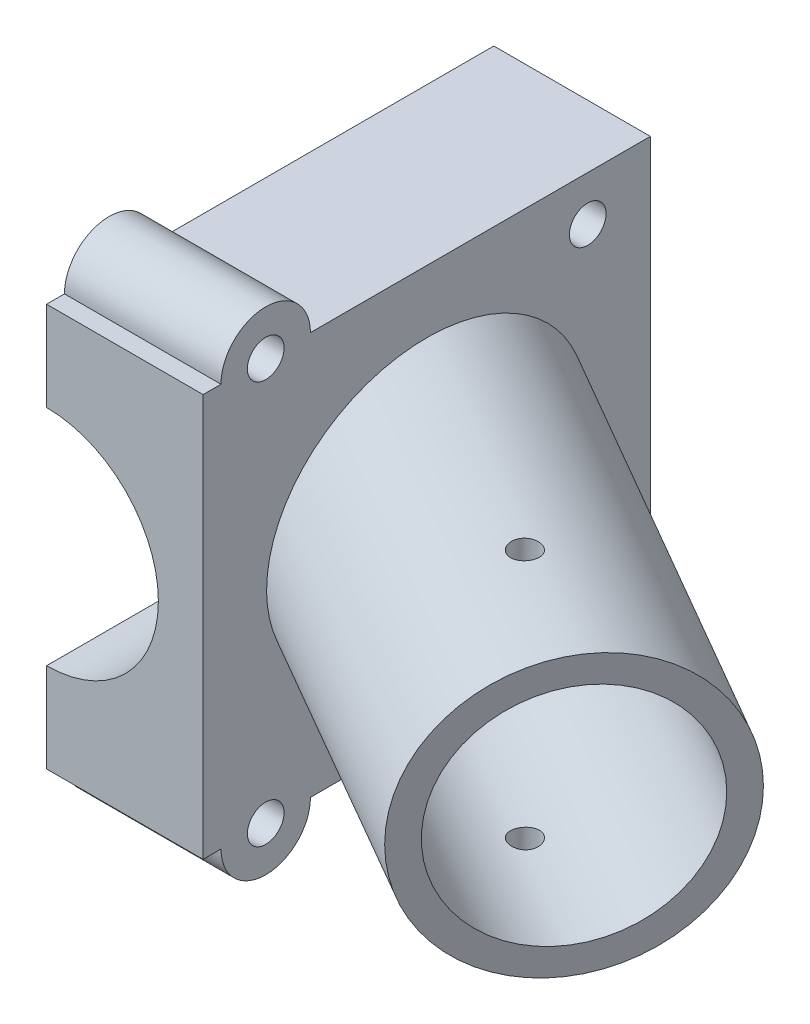
SolidWorks part; units mm, degrees
material "PLA"
ref_plane "Front Plane" through (0, 0, 0) normal (0, 0, 1) x (1, 0, 0)
ref_plane "Top Plane" through (0, 0, 0) normal (0, 1, 0) x (1, 0, 0)
ref_plane "Right Plane" through (0, 0, 0) normal (1, 0, 0) x (0, 0, -1)
sketch "Sketch1" plane through (0, 0, 0) normal (0, 0, 1) x (1, 0, 0)
  line L0 (-17.5, 22.5) -> (-17.5, 0)
  line L1 (55, 0) -> (-55, 0) construction
  line L2 (-17.5, 0) -> (17.5, 0)
  line L3 (17.5, 0) -> (17.5, 22.5)
  line L4 (-17.5, 22.5) -> (-12.5, 22.5)
  line L5 (17.5, 22.5) -> (12.5, 22.5)
  line L6 (0, -44.7868) -> (0, 44.7868) construction
  arc A0 (-12.5, 22.5) -> (12.5, 22.5) centre (0, 22.5) ccw
  dimension "D1" = 12.5
  dimension "D2" = 22.5
  dimension "D3" = 5
extrude "Boss-Extrude1" add sketch "Sketch1" along normal mid plane 50
sketch "Construct1" plane through (0, 0, 0) normal (0, 1, 0) x (1, 0, 0)
  line L0 (17.5, 0) -> (43.4808, -15) construction
  line L1 (-44.2539, 0) -> (44.2539, 0) construction
  line L2 (34.7051, -0.1998) -> (26.2756, -14.8002) construction
  line L3 (17.5, -25) -> (17.5, 25) construction
  point P6 (30.4904, -7.5)
  point P7 (30.4904, -7.5)
  dimension "D1" = 30
  dimension "D2" = 15
ref_plane "LegBuildPlane" through (26.1154, 0, 15.0777) normal (0.866, 0, 0.5) x (0.5, 0, -0.866)
sketch "Sketch5" plane through (26.1154, 0, 15.0777) normal (0.866, 0, 0.5) x (0.5, 0, -0.866)
  line L0 (-6.75, 22.5) -> (-3.75, 22.5)
  line L1 (21.25, 22.5) -> (24.25, 22.5)
  line L2 (17.1795, 0) -> (0.3205, 0) construction
  arc A0 (-3.75, 22.5) -> (21.25, 22.5) centre (8.75, 22.5) ccw
  arc A1 (-6.75, 22.5) -> (24.25, 22.5) centre (8.75, 22.5) ccw
  point P9 (8.75, 0)
  dimension "D1" = 15.5
  dimension "D2" = 12.5
  dimension "D3" = 22.5
  dimension "D4" = 0
extrude "Boss-Extrude2" add sketch "Sketch5" against normal up to surface and the other way blind 30 up to face at (17.5, 11.25, 0)
sketch "Sketch9" plane through (-17.5, 0, 0) normal (-1, 0, 0) x (0, 0, 1)
  line L2 (55, 0) -> (-55, 0) construction
  line L3 (-25, 22.5) -> (-25, 0) construction
  circle A0 centre (-18, 5) radius 2.05
  dimension "D3" = 5
  dimension "D1" = 4.1
  dimension "D4" = 7
extrude "Cut-Extrude3" cut sketch "Sketch9" against normal up to surface (35 mm away) up to face at (17.5, 12.4167, 0)
sketch "Construct2" plane through (0, 22.5, 0) normal (0, 1, 0) x (1, 0, 0)
  line L0 (20.0981, -15.9338) -> (32.5981, 5.7169) construction
  line L2 (50.2211, -33.3253) -> (17.5, -14.4338) construction
  line L3 (62.7211, -11.6747) -> (17.5, 14.4338) construction
  line L4 (17.5, 0) -> (26.3481, -5.1084) construction
  line L11 (-44.2539, 0) -> (44.2539, 0) construction
  dimension "D1" = 3
  dimension "D2" = 90
ref_plane "LegBuildPlane2" through (21.9731, 0, 12.6862) normal (0.866, 0, 0.5) x (0.5, 0, -0.866)
sketch "Sketch12" plane through (21.9731, 0, 12.6862) normal (0.866, 0, 0.5) x (0.5, 0, -0.866)
  line L0 (-3.75, 22.5) -> (21.25, 22.5)
  arc A0 (-3.75, 22.5) -> (21.25, 22.5) centre (8.75, 22.5) ccw
extrude "Boss-Extrude5" add sketch "Sketch12" against normal up to surface (17.4338 mm away) up to face at (17.5, 16.25, 0)
mirror "Mirror1" about plane through (17.5, 22.5, 25) normal (0, -1, 0) of "Boss-Extrude2", "Boss-Extrude1", "Cut-Extrude3", "Boss-Extrude5"
sketch "Sketch13" plane through (0, 0, 0) normal (0, 1, 0) x (1, 0, 0)
  line L0 (17.5, 0) -> (43.4808, -15) construction
  line L1 (48.7211, -35.9234) -> (64.2211, -9.0766) construction
  circle A0 centre (43.4808, -15) radius 1.55
  dimension "D2" = 3.1
  dimension "D1" = 15
extrude "Cut-Extrude4" cut sketch "Sketch13" along normal through all
sketch "Sketch16" plane through (0, 0, 0) normal (1, 0, 0) x (0, 0, -1)
  line L0 (55, 0) -> (-55, 0) construction
  line L1 (25, 45) -> (-25, 45)
  line L2 (25, 45) -> (25, 0)
  line L3 (25, 0) -> (-25, 0)
  line L4 (-25, 45) -> (-25, 0)
  line L5 (-25, 45) -> (-25, 0) construction
extrude "Cut-Extrude5" cut sketch "Sketch16" against normal up to surface (17.5 mm away) up to face at (-17.5, 40, -15.95)
sketch "Sketch18" plane through (0, 0, 0) normal (-1, 0, 0) x (0, 0, 1)
  line L0 (55, 0) -> (-55, 0) construction
  line L2 (13, 0) -> (23, 0)
  arc A0 (23, 0) -> (13, 0) centre (18, 0) cw
  circle A3 centre (-18, 5) radius 2.05 construction
  dimension "D3" = 5
  dimension "D1" = 36
extrude "Boss-Extrude6" add sketch "Sketch18" against normal blind 17.5
sketch "Sketch20" plane through (0, 0, 0) normal (-1, 0, 0) x (0, 0, 1)
  circle A0 centre (18, 0) radius 2.05
  dimension "D1" = 4.1
extrude "Cut-Extrude6" cut sketch "Sketch20" against normal up to surface (17.5 mm away) up to face at (17.5, 40, -15.95)
ref_plane "HolePlane" through (0, 22.5, 0) normal (0, 1, 0) x (1, 0, 0)
mirror "Mirror2" about plane through (0, 22.5, 0) normal (0, 1, 0) of "Boss-Extrude6", "Cut-Extrude6"
equation "\"TubeDiam\"= 12.5"
equation "\"D1@Sketch1\"=\"TubeDiam\""
equation "\"D2@Sketch1\"=\"ClampHeight\""
equation "\"MountLength\"= 50"
equation "\"D1@Boss-Extrude1\"=\"MountLength\""
equation "\"MountHoleSize\"=3.1"
equation "\"LipWidth\"= 5"
equation "\"D3@Sketch1\"=\"LipWidth\""
equation "\"LegDiam\"= 12.5"
equation "\"LegThickness\"= \"TubeDiam\" + 3"
equation "\"D1@Sketch5\"=\"LegThickness\""
equation "\"D2@Sketch5\"=\"TubeDiam\""
equation "\"ClampHeight\"= \"TubeDiam\" + 10"
equation "\"D3@Sketch5\"=\"ClampHeight\""
equation "\"HubHoleDist\"=7"
equation "\"HubHoleSize\"=4.1"
equation "\"D2@Sketch13\"=\"MountHoleSize\""
equation "\"D1@Sketch9\"=\"HubHoleSize\""
equation "\"D4@Sketch9\"=\"HubHoleDist\""
equation "\"D1@Sketch18\"=\"MountLength\" - 2 * \"HubHoleDist\""
equation "\"D1@Boss-Extrude6\"=\"TubeDiam\" +5"
equation "\"D1@Sketch20\"=\"HubHoleSize\""
